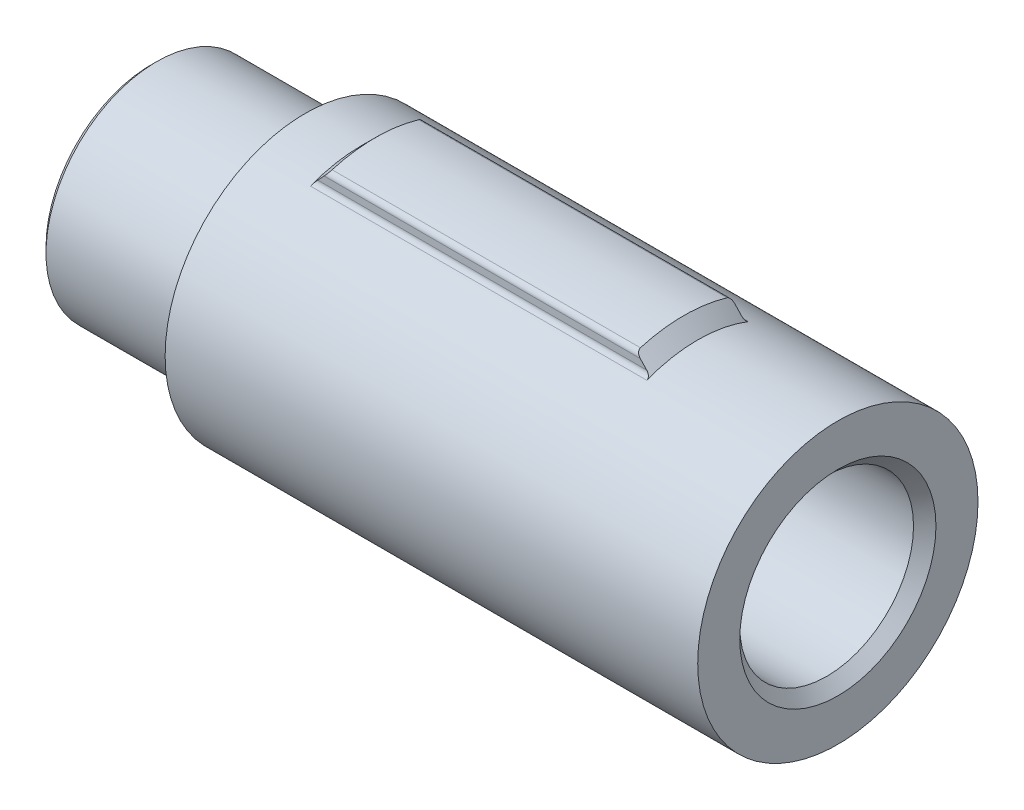
SolidWorks part; units mm, degrees
ref_plane "前视基准面" through (0, 0, 0) normal (0, 0, 1) x (1, 0, 0)
ref_plane "上视基准面" through (0, 0, 0) normal (0, 1, 0) x (1, 0, 0)
ref_plane "右视基准面" through (0, 0, 0) normal (1, 0, 0) x (0, 0, -1)
other "Configuration Table"
sketch "草图1" plane through (0, 0, 0) normal (1, 0, 0) x (0, 0, -1)
  circle A0 centre (0, 0) radius 5
  dimension "D1" = 10
extrude "凸台-拉伸1" add sketch "草图1" along normal blind 19
sketch "草图3" plane through (19, 0, 0) normal (1, 0, 0) x (0, 0, -1)
  circle A0 centre (0, 0) radius 3.1
  dimension "D1" = 6.2
extrude "切除-拉伸1" cut sketch "草图3" against normal blind 17
sketch "草图5" plane through (2, 0, 0) normal (1, 0, 0) x (0, 0, -1)
  line L1 (-1.6882, 2.6) -> (1.6882, 2.6)
  line L2 (-1.6882, 2.6) -> (-1.6882, 5.2345)
  line L3 (1.6882, 2.6) -> (1.6882, 5.2345)
  line L4 (0, 5.5) -> (1.6882, 5.5) construction
  line L5 (-1.6882, 5.5) -> (0, 5.5) construction
  line L6 (-1.6882, 5.2345) -> (-1.6882, 5.5) construction
  line L7 (1.6882, 5.2345) -> (1.6882, 5.5) construction
  circle A0 centre (0, 0) radius 3.1 construction
  arc A1 (1.6882, 2.6) -> (-1.6882, 2.6) centre (0, 0) ccw construction
  arc A2 (-1.6882, 2.6) -> (1.6882, 2.6) centre (0, 0) ccw construction
  arc A5 (-1.6882, 5.2345) -> (1.6882, 5.2345) centre (0, 0) ccw construction
  circle A6 centre (0, 0) radius 5.5
  arc A7 (1.6882, 5.2345) -> (-1.6882, 5.2345) centre (0, 0) ccw
  dimension "D1" = 2.6
  dimension "D2" = 0.5
extrude "凸台-拉伸2" add sketch "草图5" along normal blind 12
sketch "草图8" plane through (0, 0, 0) normal (-1, 0, 0) x (0, 0, 1)
  circle A0 centre (0, 0) radius 3.95
  dimension "D1" = 7.9
extrude "凸台-拉伸4" add sketch "草图8" along normal blind 5.5
sketch "草图9" plane through (-5.5, 0, 0) normal (-1, 0, 0) x (0, 0, 1)
  circle A0 centre (0, 0) radius 2.725
  dimension "D1" = 5.45
extrude "切除-拉伸2" cut sketch "草图9" against normal blind 5.5
sketch "草图10" plane through (0, 0, 0) normal (-1, 0, 0) x (0, 0, 1)
  line L1 (0.7217, 1.25) -> (-0.7217, 1.25)
  line L2 (-0.7217, 1.25) -> (-1.4434, 0)
  line L3 (-1.4434, 0) -> (-0.7217, -1.25)
  line L4 (-0.7217, -1.25) -> (0.7217, -1.25)
  line L5 (0.7217, -1.25) -> (1.4434, 0)
  line L6 (1.4434, 0) -> (0.7217, 1.25)
  circle A0 centre (0, 0) radius 1.25 construction
  dimension "D1" = 2.5
extrude "凸台-拉伸5" add sketch "草图10" along normal blind 4
fillet "圆角1" radius 0.2 4 edges at (8, 4.7064, -1.6882) (8, 5.2345, -1.6882) (8, 4.7064, 1.6882) (8, 5.2345, 1.6882)
chamfer "倒角1" distance 0.5 angle 45 3 edges at (14, 5.5, 0) (2, 5.5, 0) (14, 2.6, 0)
chamfer "倒角2" distance 0.4 angle 45 1 edges at (19, 0, -3.1)
chamfer "倒角3" distance 0.2 angle 45 8 edges at (-4, -0.625, 1.0825) (-4, -1.25, 0) (-4, -0.625, -1.0825) (-4, 0.625, -1.0825) (-4, 1.25, 0) (-4, 0.625, 1.0825) (-5.5, 0, 3.95) (-5.5, 0, 2.725)
